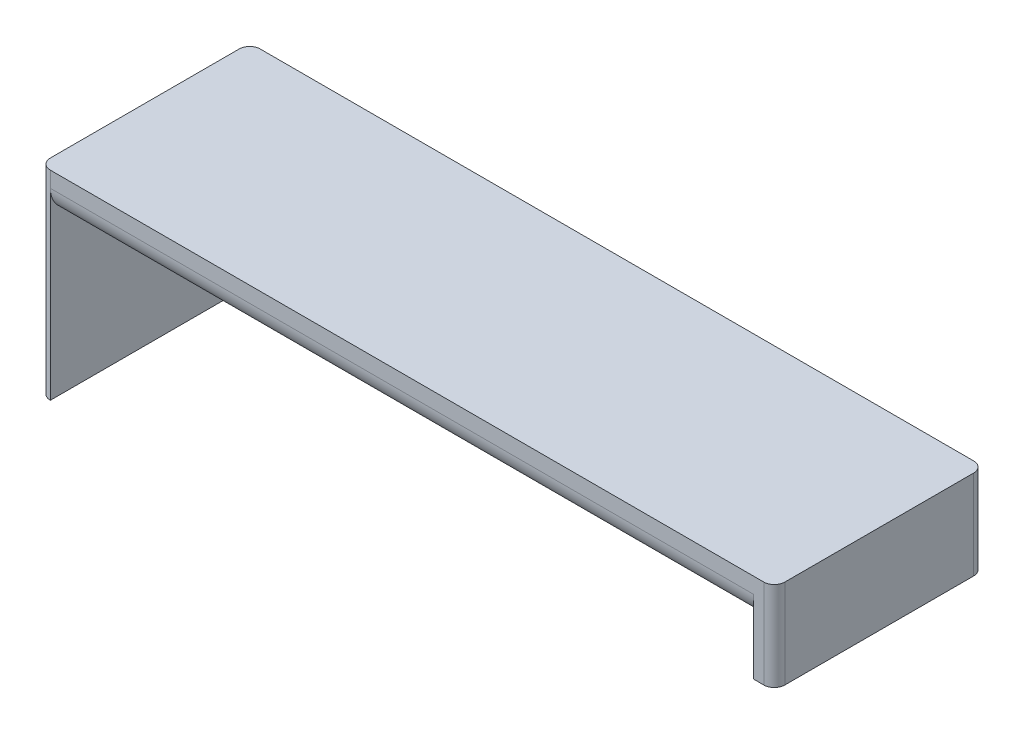
SolidWorks part; units mm, degrees
ref_plane "Front Plane" through (0, 0, 0) normal (0, 0, 1) x (1, 0, 0)
ref_plane "Top Plane" through (0, 0, 0) normal (0, 1, 0) x (1, 0, 0)
ref_plane "Right Plane" through (0, 0, 0) normal (1, 0, 0) x (0, 0, -1)
sketch "Sketch1" plane through (0, 0, 0) normal (0, 1, 0) x (1, 0, 0)
  line L1 (-70, 20) -> (70, 20)
  line L2 (-70, 20) -> (-70, -20)
  line L3 (-70, -20) -> (70, -20)
  line L4 (70, 20) -> (70, -20)
  line L5 (-70, 20) -> (70, -20) construction
  line L6 (-70, -20) -> (70, 20) construction
  line L7 (-70, 20) -> (-68, 20)
  line L8 (-70, 20) -> (-70, -20)
  line L9 (-70, -20) -> (-68, -20)
  line L10 (-68, 20) -> (-68, -20)
  line L11 (-70, 20) -> (-68, -20) construction
  line L12 (-70, -20) -> (-68, 20) construction
  line L13 (70, 20) -> (68, 20)
  line L14 (70, 20) -> (70, -20)
  line L15 (70, -20) -> (68, -20)
  line L16 (68, 20) -> (68, -20)
  line L17 (70, 20) -> (68, -20) construction
  line L18 (70, -20) -> (68, 20) construction
  point P0 (0, 0)
  point P8 (-69, 0)
  point P11 (69, 0)
  dimension "D1" = 140
  dimension "D2" = 40
  dimension "D3" = 2
  dimension "D4" = 2
extrude "Boss-Extrude1" add sketch "Sketch1" along normal blind 8 contours L16 L1 L10 L3 | L1 L16 L3 L4 | L10 L1 L2 L3 region at (-69, 0, 0) region at (0, 0, 0) region at (69, 0, 0)
extrude "Boss-Extrude2" add sketch "Sketch1<3>" against normal blind 9 contours L1 L16 L3 L4 region at (69, 0, 0)
sketch "Sketch1<3>" plane through (0, 0, 0) normal (0, 1, 0) x (1, 0, 0) same geometry as "Sketch1"
sketch "Sketch2" plane through (68, 0, 0) normal (-1, 0, 0) x (0, 0, 1)
  line L0 (-20, 0) -> (20, 0) construction
  line L1 (9.125, 0) -> (-9.125, 0)
  line L2 (9.125, 0) -> (9.125, -9)
  line L3 (9.125, -9) -> (-9.125, -9)
  line L4 (-9.125, 0) -> (-9.125, -9)
  line L5 (9.125, 0) -> (-9.125, -9) construction
  line L6 (9.125, -9) -> (-9.125, 0) construction
  line L7 (-20, -9) -> (-20, 0) construction
  line L8 (9.125, -9) -> (8.525, -9)
  line L9 (9.125, -9) -> (9.125, 0)
  line L10 (9.125, 0) -> (8.525, 0)
  line L11 (8.525, -9) -> (8.525, 0)
  line L12 (9.125, -9) -> (8.525, 0) construction
  line L13 (9.125, 0) -> (8.525, -9) construction
  line L14 (-9.125, -9) -> (-8.525, -9)
  line L15 (-9.125, -9) -> (-9.125, 0)
  line L16 (-9.125, 0) -> (-8.525, 0)
  line L17 (-8.525, -9) -> (-8.525, 0)
  line L18 (-9.125, -9) -> (-8.525, 0) construction
  line L19 (-9.125, 0) -> (-8.525, -9) construction
  line L20 (8.525, -0.6) -> (-8.525, -0.6)
  line L21 (8.525, -0.6) -> (8.525, 0)
  line L22 (8.525, 0) -> (-8.525, 0)
  line L23 (-8.525, -0.6) -> (-8.525, 0)
  line L24 (8.525, -0.6) -> (-8.525, 0) construction
  line L25 (8.525, 0) -> (-8.525, -0.6) construction
  line L26 (-9.125, -9) -> (-20, -9)
  line L27 (-9.125, -9) -> (-9.125, 0)
  line L28 (-9.125, 0) -> (-20, 0)
  line L29 (-20, -9) -> (-20, 0)
  line L30 (-9.125, -9) -> (-20, 0) construction
  line L31 (-9.125, 0) -> (-20, -9) construction
  line L33 (9.125, -9) -> (20, -9)
  line L34 (9.125, -9) -> (9.125, 0)
  line L35 (9.125, 0) -> (20, 0)
  line L36 (20, -9) -> (20, 0)
  line L37 (9.125, -9) -> (20, 0) construction
  line L38 (9.125, 0) -> (20, -9) construction
  point P4 (0, -4.5)
  point P7 (0, 0)
  point P11 (8.825, -4.5)
  point P14 (-8.825, -4.5)
  point P18 (0, -0.3)
  point P20 (-14.5625, -4.5)
  point P25 (14.5625, -4.5)
  line M3 (20, 0) -> (-20, 0)
  line M4 (-20, 0) -> (-20, -9)
  line M6 (20, -9) -> (20, 0)
  dimension "D1" = 18.25
  dimension "D2" = 9
  dimension "D3" = 0.6
  dimension "D4" = 0.6
  dimension "D5" = 0.6
extrude "Boss-Extrude3" add sketch "Sketch2" along normal blind 1 contours L2 L33 M6 M3 | L26 L4 M3 M4 region at (68, -4.5, 14.5625) region at (68, -4.5, -14.5625)
extrude "Boss-Extrude4" add sketch "Sketch2<3>" along normal blind 1 from surface contours L11 L3 L2 M3 | L2 L33 M6 M3 | L20 L11 L1 L17 | L3 L17 L4 M3 | L26 L4 M3 M4 region at (68, -4.5, 8.825) region at (68, -4.5, 14.5625) region at (68, -0.3, 0) region at (68, -4.5, -8.825) region at (68, -4.5, -14.5625) starting at face at (67, -4.5, 14.5625)
sketch "Sketch2<3>" plane through (68, 0, 0) normal (-1, 0, 0) x (0, 0, 1) same geometry as "Sketch2"
ref_plane "Plane1" through (64, 0, 0) normal (-1, 0, 0) x (0, 0, 1)
extrude "Boss-Extrude5" add sketch "Sketch1<4>" against normal blind 30 contours L10 L1 L2 L3 region at (-69, 0, 0)
sketch "Sketch1<4>" plane through (0, 0, 0) normal (0, 1, 0) x (1, 0, 0) same geometry as "Sketch1"
sketch "Sketch3" plane through (64, 0, 0) normal (-1, 0, 0) x (0, 0, 1)
  line L0 (0, 0) -> (0, -8) construction
  line L1 (11.4197, -4) -> (-11.4197, -4)
  line L2 (-11.4197, -4) -> (-11.4197, 0)
  line L3 (-11.4197, 0) -> (0, 0)
  line L4 (0, 0) -> (11.4197, 0)
  line L5 (-20, 0) -> (20, 0) construction
  line L6 (11.4197, 0) -> (11.4197, -4)
  circle A0 centre (0, -8) radius 12.1
  point P5 (0, 0)
  point P7 (0, -4)
  point P12 (-1.4598, -12.0116)
  point P13 (0, 0)
  point P14 (0, 0)
  point P15 (0, -12.1)
  point P16 (11.5105, 0)
  point P17 (0, 0)
  point P18 (0, 0)
  point P19 (0, -10.4932)
  point P20 (0, -7.2884)
  point P21 (0, 0)
  point P22 (0, -4.0126)
  dimension "D1" = 24.2
  dimension "D2" = 8
extrude "Cut-Extrude1" cut sketch "Sketch3" along normal up to surface (132 mm away) contours L1 A0 | L4 L0 L1 A0 | L0 L3 A0 L1 | L4 A0 L3 region at (64, -2.0741, 5.2329) region at (64, -2.0741, -5.2329) region at (64, 1.6664, 0) region at (64, -11.055, 0) up to face at (-68, -15, 0)
fillet "Fillet1" radius 5 2 edges at (-1, 0, 20) (-1, 0, -20)
fillet "Fillet2" radius 2 4 edges at (-70, -11, 20) (-70, -11, -20) (70, -0.5, 20) (70, -0.5, -20)
extrude "Boss-Extrude6" add sketch "Sketch3<3>" along normal up to surface and the other way up to surface contours A0 L3 L2 | A0 L6 L4 region at (64, -1.2253, 10.6935) region at (64, -1.2253, -10.6935) up to face at (-68, -5.9964, 0) other way up to face at (66, -2.9271, 0)
sketch "Sketch3<3>" plane through (64, 0, 0) normal (-1, 0, 0) x (0, 0, 1) same geometry as "Sketch3"
fillet "Fillet3" radius 0.5 2 edges at (-1, -4, -11.4197) (-1, -4, 11.4197)
fillet "Fillet4" radius 1 2 edges at (-1, 0, -11.4197) (-1, 0, 11.4197)
